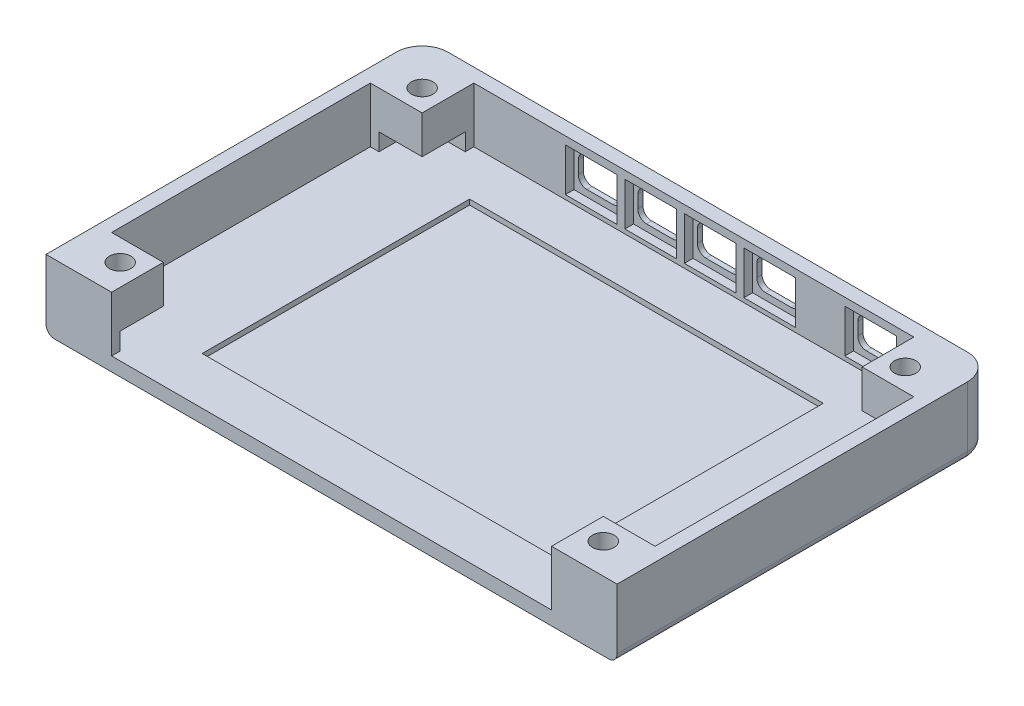
SolidWorks part; units mm, degrees
ref_plane "前视基准面" through (0, 0, 0) normal (0, 0, 1) x (1, 0, 0)
ref_plane "上视基准面" through (0, 0, 0) normal (0, 1, 0) x (1, 0, 0)
ref_plane "右视基准面" through (0, 0, 0) normal (1, 0, 0) x (0, 0, -1)
sketch "草图1" plane through (0, 0, 0) normal (0, 1, 0) x (1, 0, 0)
  line L1 (-31.5, -21) -> (31.5, -21)
  line L2 (-31.5, -21) -> (-31.5, 21)
  line L3 (-31.5, 21) -> (31.5, 21)
  line L4 (31.5, -21) -> (31.5, 21)
  line L5 (-31.5, -21) -> (31.5, 21) construction
  line L6 (-31.5, 21) -> (31.5, -21) construction
  point P0 (0, 0)
  dimension "D1" = 63
  dimension "D2" = 42
extrude "底" add sketch "草图1" against normal blind 1.6
sketch "草图2" plane through (0, 0, 0) normal (0, 1, 0) x (1, 0, 0)
  line L1 (-20.5, -15.5) -> (20.5, -15.5)
  line L2 (-20.5, -15.5) -> (-20.5, 15.5)
  line L3 (-20.5, 15.5) -> (20.5, 15.5)
  line L4 (20.5, -15.5) -> (20.5, 15.5)
  line L5 (-20.5, -15.5) -> (20.5, 15.5) construction
  line L6 (-20.5, 15.5) -> (20.5, -15.5) construction
  point P0 (0, 0)
  dimension "D1" = 41
  dimension "D2" = 31
extrude "电池槽" cut sketch "草图2" against normal blind 0.6
sketch "草图4" plane through (0, -1.6, 0) normal (0, -1, 0) x (-1, 0, 0)
  line L0 (-31.5, 21) -> (-31.5, -21)
  line L1 (-31.5, 21) -> (-33.1, 21)
  line L2 (-31.5, -21) -> (-33.1, -21)
  line L3 (-33.1, 21) -> (-33.1, -21)
  line L4 (31.5, 21) -> (31.5, -21)
  line L5 (31.5, 21) -> (33.1, 21)
  line L6 (31.5, -21) -> (33.1, -21)
  line L7 (33.1, 21) -> (33.1, -21)
  dimension "D1" = 1.6
  dimension "D2" = 1.6
extrude "侧边" add sketch "草图4" against normal blind 8
sketch "草图5" plane through (0, 0, 0) normal (0, 1, 0) x (1, 0, 0)
  line L0 (-31.5, 21) -> (-31.5, 15)
  line L1 (-31.5, 21) -> (-25.5, 21)
  line L2 (-31.5, 15) -> (-25.5, 15)
  line L3 (-25.5, 21) -> (-25.5, 15)
  line L4 (-31.5, 21) -> (-31.5, -21) construction
  line L5 (25.5, 21) -> (25.5, 15)
  line L6 (25.5, 21) -> (31.5, 21)
  line L7 (25.5, 15) -> (31.5, 15)
  line L8 (31.5, 21) -> (31.5, 15)
  line L9 (-31.5, -15) -> (-31.5, -21)
  line L10 (-31.5, -15) -> (-25.5, -15)
  line L11 (-31.5, -21) -> (-25.5, -21)
  line L12 (-25.5, -15) -> (-25.5, -21)
  line L13 (25.5, -15) -> (25.5, -21)
  line L14 (25.5, -15) -> (31.5, -15)
  line L15 (25.5, -21) -> (31.5, -21)
  line L16 (31.5, -15) -> (31.5, -21)
  dimension "D1" = 6
  dimension "D2" = 6
  dimension "D3" = 6
  dimension "D4" = 6
extrude "螺丝固定" add sketch "草图5" along normal up to surface (6.4 mm away) up to face at (-32.3, 6.4, 0)
sketch "草图6" plane through (0, 6.4, 0) normal (0, 1, 0) x (1, 0, 0)
  line L0 (-25.5, 15) -> (-25.5, 21) construction
  line L1 (-31.5, 15) -> (-25.5, 15) construction
  circle A0 centre (-28, 17.5) radius 1.25
  circle A1 centre (28, 17.5) radius 1.25
  circle A2 centre (28, -17.5) radius 1.25
  circle A3 centre (-28, -17.5) radius 1.25
  point P2 (0, 0)
  dimension "D1" = 2.5
  dimension "D2" = 2.5
  dimension "D3" = 2.5
  dimension "D4" = 2
  dimension "D5" = 2
extrude "螺丝孔" cut sketch "草图6" against normal up to surface (6.4 mm away) up to face at (0, 0, 0)
sketch "草图8" plane through (0, 0, 0) normal (0, 1, 0) x (1, 0, 0)
  line L0 (25.5, 21) -> (25.5, 15) construction
  line L1 (-30.5, 20) -> (-25.5, 20)
  line L2 (-30.5, 20) -> (-30.5, 15)
  line L3 (-30.5, 15) -> (-25.5, 15)
  line L4 (-25.5, 20) -> (-25.5, 15)
  line L5 (-30.5, 20) -> (-25.5, 15) construction
  line L6 (-30.5, 15) -> (-25.5, 20) construction
  line L7 (30.5, 20) -> (25.5, 20)
  line L8 (30.5, 20) -> (30.5, 15)
  line L9 (30.5, 15) -> (25.5, 15)
  line L10 (25.5, 20) -> (25.5, 15)
  line L11 (30.5, 20) -> (25.5, 15) construction
  line L12 (30.5, 15) -> (25.5, 20) construction
  line L14 (-30.5, -20) -> (-25.5, -20)
  line L15 (-30.5, -20) -> (-30.5, -15)
  line L16 (-30.5, -15) -> (-25.5, -15)
  line L17 (-25.5, -20) -> (-25.5, -15)
  line L18 (-30.5, -20) -> (-25.5, -15) construction
  line L19 (-30.5, -15) -> (-25.5, -20) construction
  line L20 (30.5, -20) -> (25.5, -20)
  line L21 (30.5, -20) -> (30.5, -15)
  line L22 (30.5, -15) -> (25.5, -15)
  line L23 (25.5, -20) -> (25.5, -15)
  line L24 (30.5, -20) -> (25.5, -15) construction
  line L25 (30.5, -15) -> (25.5, -20) construction
  circle A0 centre (28, 17.5) radius 1.25 construction
  circle A1 centre (28, -17.5) radius 1.25 construction
  circle A2 centre (-28, -17.5) radius 1.25 construction
  circle A3 centre (-28, 17.5) radius 1.25 construction
  circle A4 centre (28, 17.5) radius 1.25 construction
  circle A5 centre (28, -17.5) radius 1.25 construction
  circle A6 centre (-28, -17.5) radius 1.25 construction
  circle A7 centre (-28, 17.5) radius 1.25 construction
extrude "切除-拉伸4" cut sketch "草图8" along normal blind 2
sketch "草图9" plane through (0, 0, -21) normal (0, 0, -1) x (-1, 0, 0)
  line L0 (-33.1, 6.4) -> (-33.1, -1.6)
  line L1 (-33.1, 6.4) -> (33.1, 6.4)
  line L2 (-33.1, -1.6) -> (33.1, -1.6)
  line L3 (33.1, 6.4) -> (33.1, -1.6)
extrude "凸台-拉伸4" add sketch "草图9" along normal blind 1.6
sketch "草图10" plane through (0, 0, -21) normal (0, 0, 1) x (1, 0, 0)
  line L1 (17.5, 0.5) -> (23.5, 0.5)
  line L2 (17.5, 0.5) -> (17.5, 5.5)
  line L3 (17.5, 5.5) -> (23.5, 5.5)
  line L4 (23.5, 0.5) -> (23.5, 5.5)
  line L5 (17.5, 0.5) -> (23.5, 5.5) construction
  line L6 (17.5, 5.5) -> (23.5, 0.5) construction
  line L7 (25.5, 0) -> (-25.5, 0) construction
  line L8 (25.5, 6.4) -> (25.5, 0) construction
  line L9 (5.8, 0.5) -> (11.8, 0.5)
  line L10 (5.8, 0.5) -> (5.8, 5.5)
  line L11 (5.8, 5.5) -> (11.8, 5.5)
  line L12 (11.8, 0.5) -> (11.8, 5.5)
  line L13 (5.8, 0.5) -> (11.8, 5.5) construction
  line L14 (5.8, 5.5) -> (11.8, 0.5) construction
  line L15 (-1.1, 0.5) -> (4.9, 0.5)
  line L16 (-1.1, 0.5) -> (-1.1, 5.5)
  line L17 (-1.1, 5.5) -> (4.9, 5.5)
  line L18 (4.9, 0.5) -> (4.9, 5.5)
  line L19 (-1.1, 0.5) -> (4.9, 5.5) construction
  line L20 (-1.1, 5.5) -> (4.9, 0.5) construction
  line L21 (-8, 0.5) -> (-2, 0.5)
  line L22 (-8, 0.5) -> (-8, 5.5)
  line L23 (-8, 5.5) -> (-2, 5.5)
  line L24 (-2, 0.5) -> (-2, 5.5)
  line L25 (-8, 0.5) -> (-2, 5.5) construction
  line L26 (-8, 5.5) -> (-2, 0.5) construction
  line L27 (-14.9, 0.5) -> (-8.9, 0.5)
  line L28 (-14.9, 0.5) -> (-14.9, 5.5)
  line L29 (-14.9, 5.5) -> (-8.9, 5.5)
  line L30 (-8.9, 0.5) -> (-8.9, 5.5)
  line L31 (-14.9, 0.5) -> (-8.9, 5.5) construction
  line L32 (-14.9, 5.5) -> (-8.9, 0.5) construction
  point P0 (20.5, 3)
  point P11 (8.8, 3)
  point P16 (1.9, 3)
  point P21 (-5, 3)
  point P26 (-11.9, 3)
  dimension "D1" = 6
  dimension "D2" = 5
  dimension "D3" = 5
  dimension "D4" = 3
  dimension "D5" = 2
  dimension "D6" = 4
extrude "切除-拉伸5" cut sketch "草图10" against normal blind 1
sketch "草图12" plane through (0, 0, -22) normal (0, 0, 1) x (1, 0, 0)
  line L0 (17.5, 5.5) -> (23.5, 0.5) construction
  line L1 (6.3, 2.2668) -> (6.3, 3.7332)
  line L2 (19, 1.2668) -> (22, 1.2668)
  line L3 (18, 2.2668) -> (18, 3.7332)
  line L4 (23.5, 0.5) -> (23.5, 5.5)
  line L5 (23.5, 5.5) -> (17.5, 5.5)
  line L6 (17.5, 5.5) -> (17.5, 0.5)
  line L7 (17.5, 0.5) -> (23.5, 0.5)
  line L8 (23.5, 0.5) -> (23.5, 5.5) construction
  line L9 (23.5, 5.5) -> (17.5, 5.5) construction
  line L10 (17.5, 5.5) -> (17.5, 0.5) construction
  line L11 (17.5, 0.5) -> (23.5, 0.5) construction
  line L12 (19, 4.7332) -> (22, 4.7332)
  line L13 (23, 2.2668) -> (23, 3.7332)
  line L14 (18, 1.2668) -> (23, 4.7332) construction
  line L15 (18, 4.7332) -> (23, 1.2668) construction
  line L16 (7.3, 1.2668) -> (10.3, 1.2668)
  line L17 (7.3, 4.7332) -> (10.3, 4.7332)
  line L18 (11.3, 2.2668) -> (11.3, 3.7332)
  line L19 (-0.6, 2.2668) -> (-0.6, 3.7332)
  line L20 (0.4, 1.2668) -> (3.4, 1.2668)
  line L21 (0.4, 4.7332) -> (3.4, 4.7332)
  line L22 (4.4, 2.2668) -> (4.4, 3.7332)
  line L23 (-7.5, 2.2668) -> (-7.5, 3.7332)
  line L24 (-6.5, 1.2668) -> (-3.5, 1.2668)
  line L25 (-6.5, 4.7332) -> (-3.5, 4.7332)
  line L26 (-2.5, 2.2668) -> (-2.5, 3.7332)
  line L27 (-14.4, 2.2668) -> (-14.4, 3.7332)
  line L28 (-13.4, 1.2668) -> (-10.4, 1.2668)
  line L29 (-13.4, 4.7332) -> (-10.4, 4.7332)
  line L30 (-9.4, 2.2668) -> (-9.4, 3.7332)
  arc A0 (22, 4.7332) -> (23, 3.7332) centre (22, 3.7332) cw
  arc A1 (22, 1.2668) -> (23, 2.2668) centre (22, 2.2668) ccw
  arc A2 (19, 1.2668) -> (18, 2.2668) centre (19, 2.2668) cw
  arc A3 (18, 3.7332) -> (19, 4.7332) centre (19, 3.7332) cw
  arc A4 (6.3, 3.7332) -> (7.3, 4.7332) centre (7.3, 3.7332) cw
  arc A5 (7.3, 1.2668) -> (6.3, 2.2668) centre (7.3, 2.2668) cw
  arc A6 (10.3, 4.7332) -> (11.3, 3.7332) centre (10.3, 3.7332) cw
  arc A7 (10.3, 1.2668) -> (11.3, 2.2668) centre (10.3, 2.2668) ccw
  arc A8 (-0.6, 3.7332) -> (0.4, 4.7332) centre (0.4, 3.7332) cw
  arc A9 (0.4, 1.2668) -> (-0.6, 2.2668) centre (0.4, 2.2668) cw
  arc A10 (3.4, 4.7332) -> (4.4, 3.7332) centre (3.4, 3.7332) cw
  arc A11 (3.4, 1.2668) -> (4.4, 2.2668) centre (3.4, 2.2668) ccw
  arc A12 (-7.5, 3.7332) -> (-6.5, 4.7332) centre (-6.5, 3.7332) cw
  arc A13 (-6.5, 1.2668) -> (-7.5, 2.2668) centre (-6.5, 2.2668) cw
  arc A14 (-3.5, 4.7332) -> (-2.5, 3.7332) centre (-3.5, 3.7332) cw
  arc A15 (-3.5, 1.2668) -> (-2.5, 2.2668) centre (-3.5, 2.2668) ccw
  arc A16 (-14.4, 3.7332) -> (-13.4, 4.7332) centre (-13.4, 3.7332) cw
  arc A17 (-13.4, 1.2668) -> (-14.4, 2.2668) centre (-13.4, 2.2668) cw
  arc A18 (-10.4, 4.7332) -> (-9.4, 3.7332) centre (-10.4, 3.7332) cw
  arc A19 (-10.4, 1.2668) -> (-9.4, 2.2668) centre (-10.4, 2.2668) ccw
  point P2 (20.5, 3)
  dimension "D4" = 1
  dimension "D2" = 5
  dimension "D3" = 3.4664
  dimension "D1" = 0
  dimension "D5" = 2
  dimension "D6" = 4
extrude "切除-拉伸6" cut sketch "草图12" against normal up to next
fillet "圆角4" radius 1 3 edges at (-33.1, -1.6, -0.8) (33.1, -1.6, -0.8) (0, -1.6, -22.6)
fillet "圆角5" radius 3 4 edges at (-32.8071, -1.3071, -22.3071) (32.8071, -1.3071, -22.3071) (33.1, 2.9, -22.6) (-33.1, 2.9, -22.6)
sketch "草图15" plane through (0, 6.4, 0) normal (0, 1, 0) x (1, 0, 0)
  line L16 (33.1, -21) -> (33.1, 19.6)
  line L17 (30.1, 22.6) -> (-30.1, 22.6)
  line L18 (-33.1, 19.6) -> (-33.1, -21)
  line L19 (-33.1, -21) -> (-25.5, -21)
  line L20 (-25.5, -21) -> (-25.5, -15)
  line L21 (-25.5, -15) -> (-31.5, -15)
  line L22 (-31.5, -15) -> (-31.5, 15)
  line L23 (-31.5, 15) -> (-25.5, 15)
  line L24 (-25.5, 15) -> (-25.5, 21)
  line L25 (-25.5, 21) -> (25.5, 21)
  line L26 (25.5, 21) -> (25.5, 15)
  line L27 (25.5, 15) -> (31.5, 15)
  line L28 (31.5, 15) -> (31.5, -15)
  line L29 (31.5, -15) -> (25.5, -15)
  line L30 (25.5, -15) -> (25.5, -21)
  line L31 (25.5, -21) -> (33.1, -21)
  line L32 (33.1, -21) -> (33.1, 19.6)
  line L33 (30.1, 22.6) -> (-30.1, 22.6)
  line L34 (-33.1, 19.6) -> (-33.1, -21)
  line L35 (-33.1, -21) -> (-25.5, -21)
  line L36 (-25.5, -21) -> (-25.5, -15)
  line L37 (-25.5, -15) -> (-31.5, -15)
  line L38 (-31.5, -15) -> (-31.5, 15)
  line L39 (-31.5, 15) -> (-25.5, 15)
  line L40 (-25.5, 15) -> (-25.5, 21)
  line L41 (-25.5, 21) -> (25.5, 21)
  line L42 (25.5, 21) -> (25.5, 15)
  line L43 (25.5, 15) -> (31.5, 15)
  line L44 (31.5, 15) -> (31.5, -15)
  line L45 (31.5, -15) -> (25.5, -15)
  line L46 (25.5, -15) -> (25.5, -21)
  line L47 (25.5, -21) -> (33.1, -21)
  arc A2 (33.1, 19.6) -> (30.1, 22.6) centre (30.1, 19.6) ccw
  arc A3 (-30.1, 22.6) -> (-33.1, 19.6) centre (-30.1, 19.6) ccw
  arc A4 (33.1, 19.6) -> (30.1, 22.6) centre (30.1, 19.6) ccw
  arc A5 (-30.1, 22.6) -> (-33.1, 19.6) centre (-30.1, 19.6) ccw
  dimension "D1" = 0
